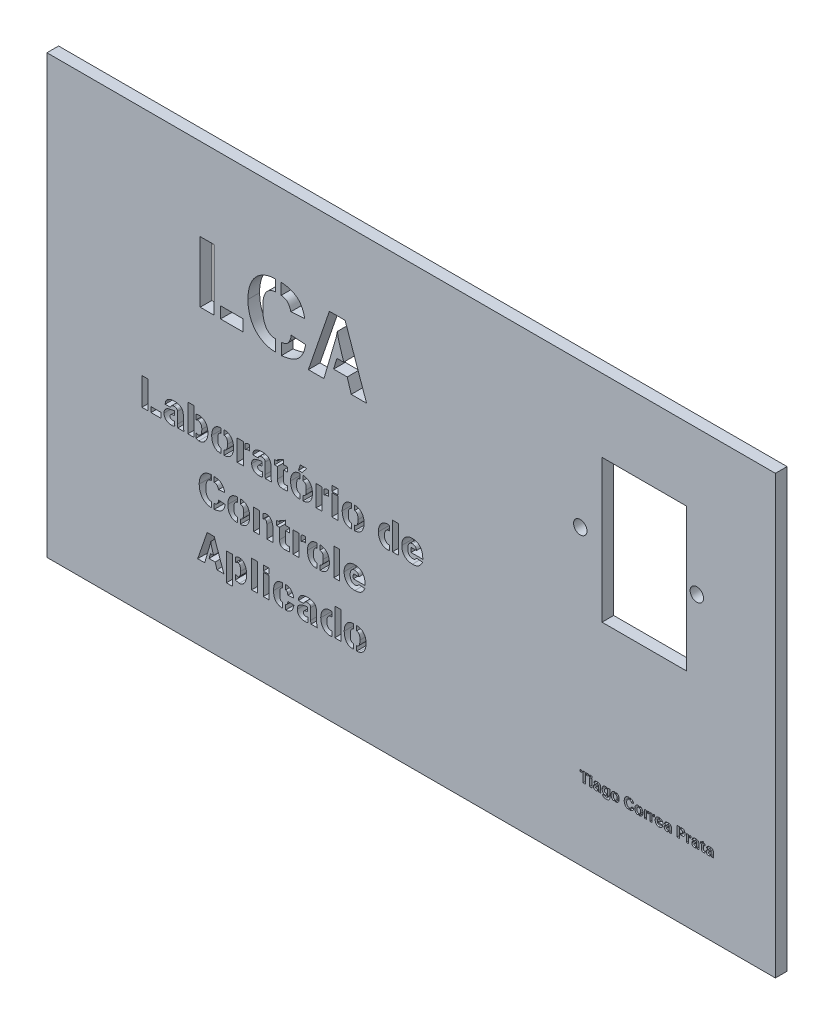
SolidWorks part; units mm, degrees
ref_plane "Front Plane" through (0, 0, 0) normal (0, 0, 1) x (1, 0, 0)
ref_plane "Top Plane" through (0, 0, 0) normal (0, 1, 0) x (1, 0, 0)
ref_plane "Right Plane" through (0, 0, 0) normal (1, 0, 0) x (0, 0, -1)
sketch "Sketch1" plane through (0, 0, 0) normal (0, 0, 1) x (1, 0, 0)
  line L1 (-112.8247, 64.3669) -> (137.1753, 64.3669)
  line L2 (-112.8247, 64.3669) -> (-112.8247, -85.6331)
  line L3 (-112.8247, -85.6331) -> (137.1753, -85.6331)
  line L4 (137.1753, 64.3669) -> (137.1753, -85.6331)
  dimension "D1" = 250
  dimension "D2" = 150
extrude "Boss-Extrude1" add sketch "Sketch1" along normal blind 4
sketch "Sketch2" plane through (0, 0, 4) normal (0, 0, 1) x (1, 0, 0)
  line L1 (77.6753, 39.3669) -> (106.6753, 39.3669)
  line L2 (77.6753, 39.3669) -> (77.6753, -9.6331)
  line L3 (77.6753, -9.6331) -> (106.6753, -9.6331)
  line L4 (106.6753, 39.3669) -> (106.6753, -9.6331)
  circle A0 centre (70.2084, 14.8669) radius 2.3
  circle A1 centre (110.2084, 14.8669) radius 2.3
  point P8 (77.6753, 14.8669)
  dimension "D3" = 40
  dimension "D1" = 29
  dimension "D2" = 49
extrude "Cut-Extrude1" cut sketch "Sketch2" against normal blind 4
sketch "Sketch4" plane through (0, 0, 4) normal (0, 0, 1) x (1, 0, 0)
  line L0 (49.1715, 64.3669) -> (49.1715, -85.6331) construction
  line L1 (-7.127, -60.6315) -> (49.1715, -60.6315) construction
  line L2 (137.1753, 64.3669) -> (-112.8247, 64.3669) construction
  line L3 (-112.8247, -85.6331) -> (137.1753, -85.6331) construction
  line L4 (49.1715, 15.0348) -> (-112.8247, 15.0348) construction
  line L5 (-112.8247, 64.3669) -> (-112.8247, -85.6331) construction
  line L6 (49.1715, -24.7136) -> (-112.8247, -24.7136) construction
  line L7 (49.1715, -60.6315) -> (137.1753, -60.6315) construction
  line L8 (137.1753, -85.6331) -> (137.1753, 64.3669) construction
  text T0 "LCA" font "Stencilia-A" height in points 80
  text T1 "Laboratório de\r\nControle\r\nAplicado" font "Stencilia-A" height in points 36
  text T2 "Tiago Correa Prata" font "Stencilia-A" height 3.5
extrude "Cut-Extrude2" cut sketch "Sketch4" against normal blind 4
